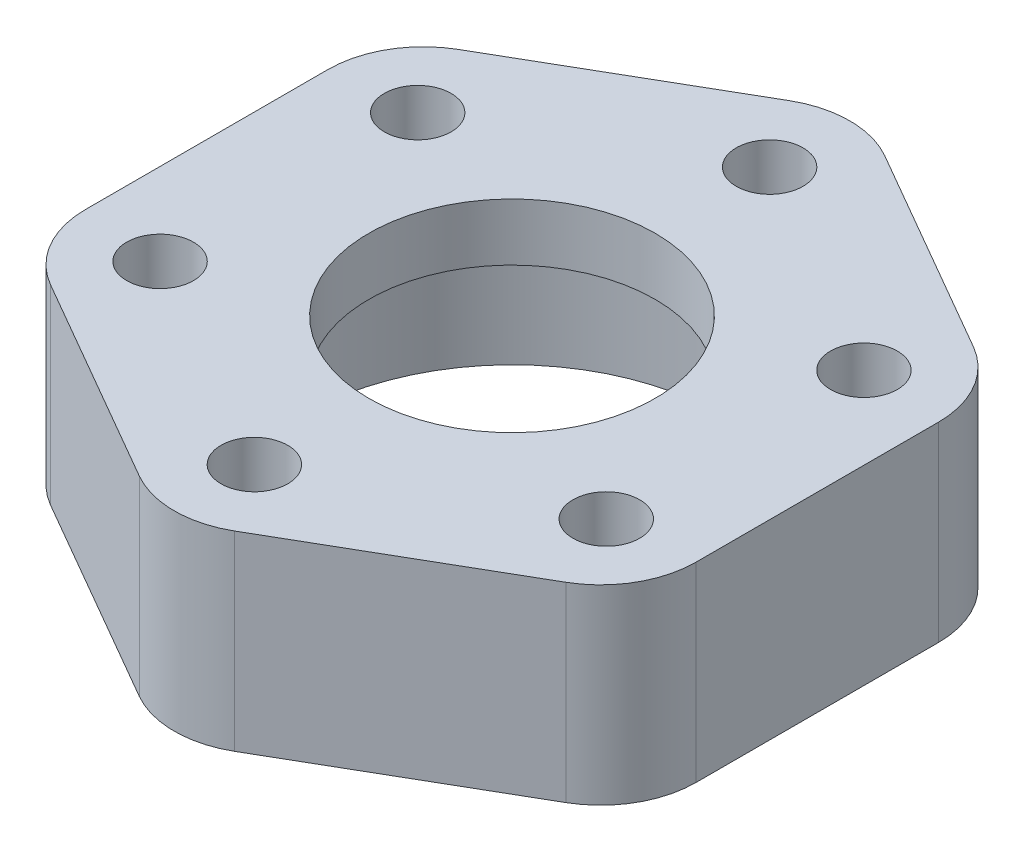
SolidWorks part; units mm, degrees
ref_plane "Front Plane" through (0, 0, 0) normal (0, 0, 1) x (1, 0, 0)
ref_plane "Top Plane" through (0, 0, 0) normal (0, 1, 0) x (1, 0, 0)
ref_plane "Right Plane" through (0, 0, 0) normal (1, 0, 0) x (0, 0, -1)
sketch "Sketch1" plane through (0, 0, 0) normal (0, 1, 0) x (1, 0, 0)
  line L1 (-2.5, 17.0318) -> (-13.5, 10.681)
  line L2 (-16, 6.3509) -> (-16, -6.3509)
  line L3 (-13.5, -10.681) -> (-2.5, -17.0318)
  line L4 (2.5, -17.0318) -> (13.5, -10.681)
  line L5 (16, -6.3509) -> (16, 6.3509)
  line L6 (13.5, 10.681) -> (2.5, 17.0318)
  circle A0 centre (0, 0) radius 11
  circle A1 centre (0, 0) radius 13.5 construction
  circle A2 centre (0, 0) radius 16 construction
  circle A3 centre (0, 13.5) radius 1.75
  circle A4 centre (11.6913, 6.75) radius 1.75
  circle A5 centre (11.6913, -6.75) radius 1.75
  circle A6 centre (0, -13.5) radius 1.75
  circle A7 centre (-11.6913, -6.75) radius 1.75
  circle A8 centre (-11.6913, 6.75) radius 1.75
  circle A9 centre (0, 0) radius 16 construction
  arc A10 (-13.5, 10.681) -> (-16, 6.3509) centre (-11, 6.3509) ccw
  arc A11 (-16, -6.3509) -> (-13.5, -10.681) centre (-11, -6.3509) ccw
  arc A12 (-2.5, -17.0318) -> (2.5, -17.0318) centre (0, -12.7017) ccw
  arc A13 (13.5, -10.681) -> (16, -6.3509) centre (11, -6.3509) ccw
  arc A14 (16, 6.3509) -> (13.5, 10.681) centre (11, 6.3509) ccw
  arc A15 (-2.5, 17.0318) -> (2.5, 17.0318) centre (0, 12.7017) cw
  point P19 (0, 0)
  dimension "D1" = 22
  dimension "D2" = 27
  dimension "D3" = 32
  dimension "D4" = 3.5
  dimension "D6" = 5
  dimension "D5" = 6
extrude "Boss-Extrude1" add sketch "Sketch1" along normal blind 10
sketch "Sketch2" plane through (0, 10, 0) normal (0, 1, 0) x (1, 0, 0)
  circle A0 centre (0, 0) radius 11
  circle A1 centre (0, 0) radius 7.5
  dimension "D1" = 15
extrude "Boss-Extrude2" add sketch "Sketch2" against normal blind 3
